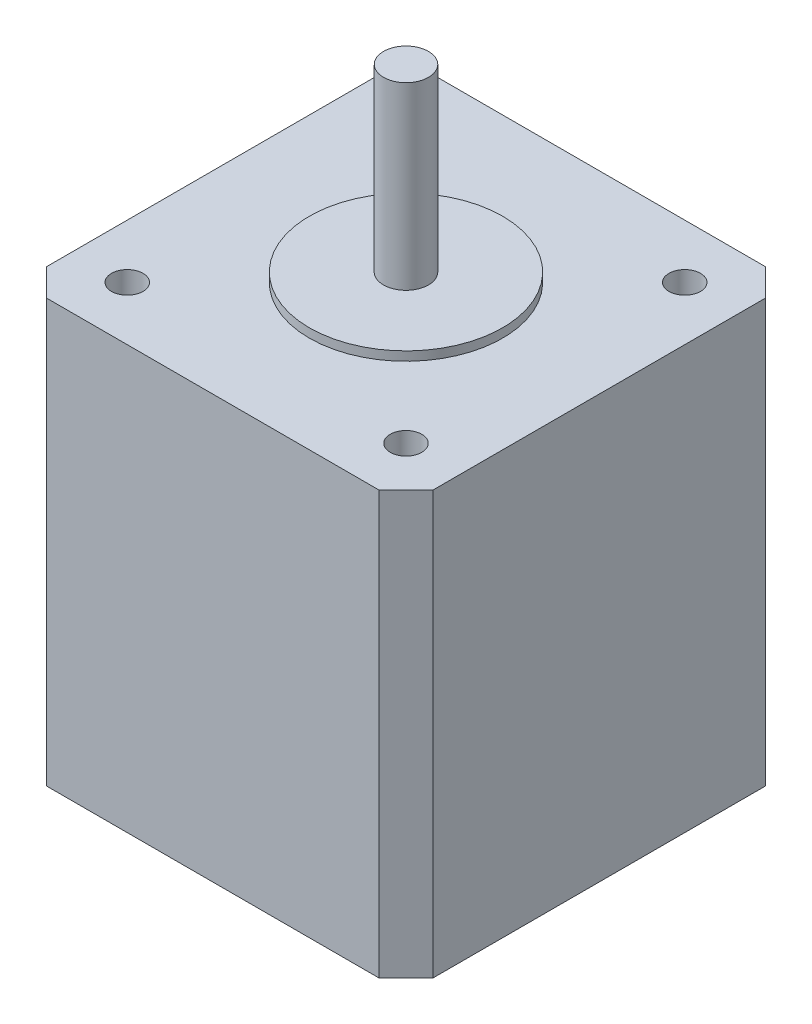
SolidWorks part; units mm, degrees
ref_plane "Front Plane" through (0, 0, 0) normal (0, 0, 1) x (1, 0, 0)
ref_plane "Top Plane" through (0, 0, 0) normal (0, 1, 0) x (1, 0, 0)
ref_plane "Right Plane" through (0, 0, 0) normal (1, 0, 0) x (0, 0, -1)
sketch "Sketch1" plane through (0, 0, 0) normal (0, 1, 0) x (1, 0, 0)
  line L1 (0, 0) -> (43, 0)
  line L2 (0, 0) -> (0, 43)
  line L3 (0, 43) -> (43, 43)
  line L4 (43, 0) -> (43, 43)
  dimension "D1" = 43
  dimension "D2" = 43
extrude "Boss-Extrude1" add sketch "Sketch1" along normal blind 47
sketch "Sketch2" plane through (0, 47, 0) normal (0, 1, 0) x (1, 0, 0)
  line L0 (0, 43) -> (43, 0) construction
  circle A0 centre (21.5, 21.5) radius 10.75
  point P6 (21.7507, 21.2493)
  point P7 (0, 0)
  dimension "D1" = 21.5
extrude "Boss-Extrude2" add sketch "Sketch2" along normal blind 1
sketch "Sketch3" plane through (0, 48, 0) normal (0, 1, 0) x (1, 0, 0)
  circle A0 centre (21.5, 21.5) radius 2.5
  circle A1 centre (21.5, 21.5) radius 10.75 construction
  point P2 (22.4177, 22.4894)
  dimension "D1" = 5
extrude "Boss-Extrude3" add sketch "Sketch3" along normal blind 20
chamfer "Chamfer1" distance 3 angle 45 4 edges at (0, 23.5, -43) (43, 23.5, -43) (43, 23.5, 0) (0, 23.5, 0)
sketch "Sketch4" plane through (0, 47, 0) normal (0, 1, 0) x (1, 0, 0)
  line L1 (6, 6) -> (37, 6) construction
  line L2 (6, 6) -> (6, 37) construction
  line L3 (6, 37) -> (37, 37) construction
  line L4 (37, 6) -> (37, 37) construction
  line L5 (0, 0) -> (41.5, 41.5) construction
  line L6 (43, 40) -> (40, 43) construction
  line L7 (1.5, 41.5) -> (41.5, 1.5) construction
  line L8 (3, 43) -> (0, 40) construction
  line L9 (40, 0) -> (43, 3) construction
  circle A2 centre (6, 37) radius 1.75
  circle A3 centre (6, 6) radius 1.75
  circle A4 centre (37, 6) radius 1.75
  circle A5 centre (37, 37) radius 1.75
  dimension "D1" = 31
  dimension "D3" = 3.5
  dimension "D4" = 3.5
  dimension "D5" = 3.5
  dimension "D6" = 3.5
  dimension "D2" = 31
extrude "Cut-Extrude2" cut sketch "Sketch4" against normal blind 10
